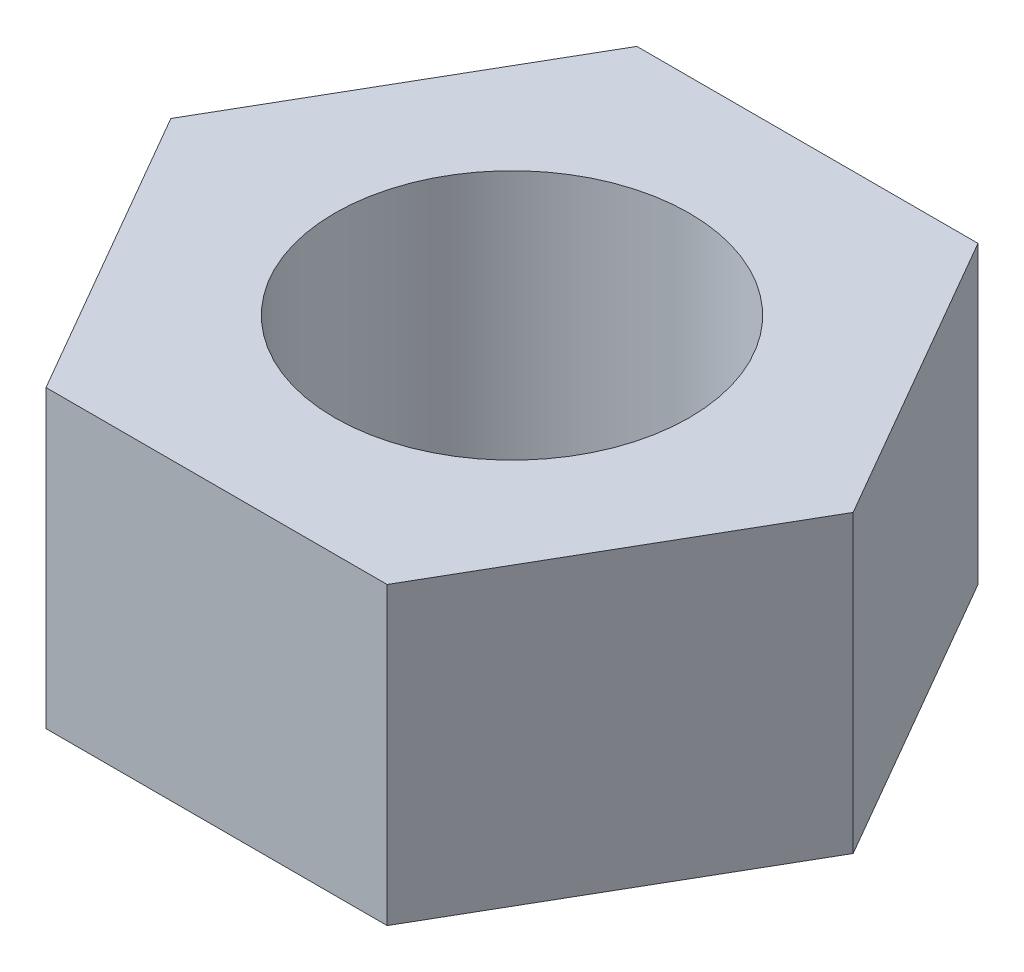
SolidWorks part; units mm, degrees
ref_plane "Front Plane" through (0, 0, 0) normal (0, 0, 1) x (1, 0, 0)
ref_plane "Top Plane" through (0, 0, 0) normal (0, 1, 0) x (1, 0, 0)
ref_plane "Right Plane" through (0, 0, 0) normal (1, 0, 0) x (0, 0, -1)
sketch "Sketch1" plane through (0, 0, 0) normal (0, 1, 0) x (1, 0, 0)
  line L1 (5.7735, 0) -> (2.8868, 5)
  line L2 (2.8868, 5) -> (-2.8868, 5)
  line L3 (-2.8868, 5) -> (-5.7735, 0)
  line L4 (-5.7735, 0) -> (-2.8868, -5)
  line L5 (-2.8868, -5) -> (2.8868, -5)
  line L6 (2.8868, -5) -> (5.7735, 0)
  circle A0 centre (0, 0) radius 5 construction
  dimension "D1" = 10
extrude "Bolt head" add sketch "Sketch1" along normal blind 5
sketch "Sketch2" plane through (0, 0, 0) normal (0, 1, 0) x (1, 0, 0)
  circle A0 centre (0, 0) radius 3
  dimension "D1" = 6
extrude "Bolt shank" [suppressed] add sketch "Sketch2" along normal blind 108
extrude "Cut-Extrude1" cut sketch "Sketch2<2>" along normal through all
sketch "Sketch2<2>" plane through (0, 0, 0) normal (0, 1, 0) x (1, 0, 0) same geometry as "Sketch2"
